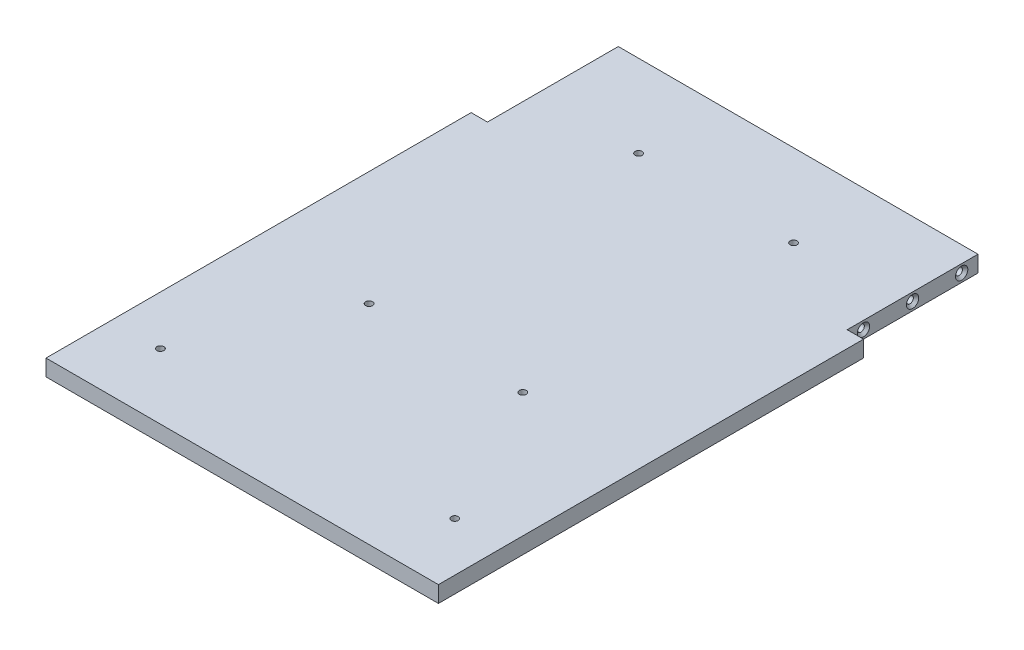
SolidWorks part; units mm, degrees
ref_plane "Front Plane" through (0, 0, 0) normal (0, 0, 1) x (1, 0, 0)
ref_plane "Top Plane" through (0, 0, 0) normal (0, 1, 0) x (1, 0, 0)
ref_plane "Right Plane" through (0, 0, 0) normal (1, 0, 0) x (0, 0, -1)
sketch "Sketch1" plane through (0, 0, 0) normal (0, 1, 0) x (1, 0, 0)
  line L0 (-6.35, 0) -> (-6.35, -50.8)
  line L1 (-6.35, 0) -> (-146.05, 0)
  line L2 (0, -50.8) -> (0, -215.9)
  line L3 (0, -215.9) -> (-152.4, -215.9)
  line L4 (-152.4, -50.8) -> (-152.4, -215.9)
  line L5 (-6.35, -50.8) -> (0, -50.8)
  line L6 (-146.05, 0) -> (-146.05, -50.8)
  line L7 (-146.05, -50.8) -> (-152.4, -50.8)
  point P7 (-3.175, -50.8)
  dimension "D1" = 152.4
  dimension "D2" = 215.9
  dimension "D3" = 50.8
  dimension "D4" = 6.35
  dimension "D5" = 6.35
  dimension "D6" = 50.8
extrude "Boss-Extrude1" add sketch "Sketch1" along normal blind 6.35
sketch "Sketch2" plane through (-6.35, 0, 0) normal (1, 0, 0) x (0, 0, -1)
  line L0 (-50.8, 6.35) -> (-50.8, 0) construction
  line L1 (-50.8, 6.35) -> (-50.8, 0) construction
  line L2 (-50.8, 0) -> (0, 0) construction
  circle A0 centre (-44.45, 3.175) radius 1.8288
  circle A1 centre (-25.4, 3.175) radius 1.8288
  circle A2 centre (-6.35, 3.175) radius 1.8288
  dimension "D4" = 3.175
  dimension "D5" = 3.175
  dimension "D6" = 3.6576
  dimension "D7" = 3.6576
  dimension "D8" = 3.6576
  dimension "D1" = 6.35
  dimension "D2" = 25.4
  dimension "D3" = 44.45
hole_wizard "#6-32 Tapped Hole1" positions "Sketch3" profile "Sketch4" tap size "#6-32" standard "ANSI Inch"
sketch "Sketch3" plane through (-6.35, 0, 0) normal (1, 0, 0) x (0, 0, -1)
  point P0 (-44.45, 3.175)
  point P3 (-25.4, 3.175)
  point P6 (-6.35, 3.175)
sketch "Sketch4" plane through (-6.35, 3.175, 44.45) normal (0, 1, 0) x (0, 0, -1)
  line L0 (0, 0) -> (0, 12.7)
  line L1 (0, 12.7) -> (1.3525, 11.8873)
  line L2 (1.3525, 11.8873) -> (1.3525, 1.0351)
  line L3 (1.3525, 1.0351) -> (2.3876, 0)
  line L5 (2.3876, 0) -> (0, 0)
  line L6 (-1.3525, 1.0351) -> (-2.3876, 0) construction
  line L10 (0, 12.7) -> (-1.3526, 11.8873) construction
  line L11 (0, -6.35) -> (0, 107.95) construction
  dimension "Tap Drill Dia." = 2.7051
  dimension "Tap Drill Depth" = 12.7
  dimension "Near C'Sink Dia." = 4.7752
  dimension "Near C'Sink Angle" = 90
  dimension "Drill Angle" = 118
cosmetic thread "Hole Thread1"
cosmetic thread "Hole Thread2"
cosmetic thread "Hole Thread3"
sketch "Sketch5" plane through (-146.05, 0, 0) normal (-1, 0, 0) x (0, 0, 1)
  circle A0 centre (6.35, 3.175) radius 1.8288
  circle A1 centre (25.4, 3.175) radius 1.8288
  circle A2 centre (44.45, 3.175) radius 1.8288
  dimension "D1" = 3.6576
  dimension "D2" = 3.6576
  dimension "D3" = 3.6576
hole_wizard "#6-32 Tapped Hole2" positions "Sketch6" profile "Sketch7" tap size "#6-32" standard "ANSI Inch"
sketch "Sketch6" plane through (-146.05, 0, 0) normal (-1, 0, 0) x (0, 0, 1)
  point P0 (6.35, 3.175)
  point P3 (25.4, 3.175)
  point P6 (44.45, 3.175)
sketch "Sketch7" plane through (-146.05, 3.175, 6.35) normal (0, 1, 0) x (0, 0, 1)
  line L0 (0, 0) -> (0, 12.7)
  line L1 (0, 12.7) -> (1.3525, 11.8873)
  line L2 (1.3525, 11.8873) -> (1.3525, 1.0351)
  line L3 (1.3525, 1.0351) -> (2.3876, 0)
  line L5 (2.3876, 0) -> (0, 0)
  line L6 (-1.3525, 1.0351) -> (-2.3876, 0) construction
  line L10 (0, 12.7) -> (-1.3526, 11.8873) construction
  line L11 (0, -6.35) -> (0, 107.95) construction
  dimension "Tap Drill Dia." = 2.7051
  dimension "Tap Drill Depth" = 12.7
  dimension "Near C'Sink Dia." = 4.7752
  dimension "Near C'Sink Angle" = 90
  dimension "Drill Angle" = 118
cosmetic thread "Hole Thread4"
cosmetic thread "Hole Thread5"
cosmetic thread "Hole Thread6"
sketch "Sketch8" plane through (0, 6.35, 0) normal (0, 1, 0) x (1, 0, 0)
  line L0 (0, -215.9) -> (0, -50.8) construction
  line L1 (-152.4, -215.9) -> (0, -215.9) construction
  circle A0 centre (-48.26, -134.874) radius 1.8288
  circle A1 centre (-107.95, -134.874) radius 1.8288
  dimension "D1" = 48.26
  dimension "D2" = 81.026
  dimension "D3" = 59.69
  dimension "D4" = 81.026
  dimension "D5" = 3.6576
  dimension "D6" = 3.6576
sketch "Sketch9" plane through (0, 6.35, 0) normal (0, 1, 0) x (1, 0, 0)
  line L0 (-152.4, -215.9) -> (0, -215.9) construction
  line L1 (-152.4, -50.8) -> (-152.4, -215.9) construction
  circle A0 centre (-133.35, -190.5) radius 1.8288
  circle A1 centre (-19.05, -190.5) radius 1.8288
  dimension "D1" = 114.3
  dimension "D2" = 25.4
  dimension "D3" = 19.05
  dimension "D4" = 3.6576
  dimension "D5" = 3.6576
hole_wizard "#6-32 Tapped Hole3" positions "Sketch12" profile "Sketch13" tap size "#6-32" standard "ANSI Inch" end condition up to next
sketch "Sketch12" plane through (0, 6.35, 0) normal (0, 1, 0) x (1, 0, 0)
  point P0 (-133.35, -190.5)
  point P3 (-19.05, -190.5)
sketch "Sketch13" plane through (-133.35, 6.35, 190.5) normal (1, 0, 0) x (0, 0, 1)
  line L0 (0, 0) -> (0, 6.35)
  line L1 (0, 6.35) -> (1.3525, 6.35)
  line L2 (1.3525, 6.35) -> (1.3525, 0)
  line L5 (1.3525, 0) -> (0, 0)
  line L11 (0, -6.35) -> (0, 107.95) construction
  dimension "Thru Tap Drill Dia." = 2.7051
  dimension "Thru Tap Drill Depth" = 6.35
cosmetic thread "Hole Thread7"
cosmetic thread "Hole Thread8"
hole_wizard "#6-32 Tapped Hole4" positions "Sketch14" profile "Sketch15" tap size "#6-32" standard "ANSI Inch" end condition up to next
sketch "Sketch14" plane through (0, 6.35, 0) normal (0, 1, 0) x (1, 0, 0)
  point P0 (-107.95, -134.874)
  point P3 (-48.26, -134.874)
sketch "Sketch15" plane through (-107.95, 6.35, 134.874) normal (1, 0, 0) x (0, 0, 1)
  line L0 (0, 0) -> (0, 6.35)
  line L1 (0, 6.35) -> (1.3525, 6.35)
  line L2 (1.3525, 6.35) -> (1.3525, 0)
  line L5 (1.3525, 0) -> (0, 0)
  line L11 (0, -6.35) -> (0, 107.95) construction
  dimension "Thru Tap Drill Dia." = 2.7051
  dimension "Thru Tap Drill Depth" = 6.35
cosmetic thread "Hole Thread9"
cosmetic thread "Hole Thread10"
sketch "Sketch16" plane through (0, 6.35, 0) normal (0, 1, 0) x (1, 0, 0)
  line L0 (-6.35, -50.8) -> (-6.35, 0) construction
  line L1 (-6.35, 0) -> (-146.05, 0) construction
  circle A0 centre (-45.974, -32.004) radius 1.8288
  circle A1 centre (-106.172, -32.004) radius 1.8288
  dimension "D1" = 39.624
  dimension "D2" = 32.004
  dimension "D3" = 60.198
  dimension "D4" = 32.004
  dimension "D5" = 3.6576
  dimension "D6" = 3.6576
hole_wizard "#6-32 Tapped Hole5" positions "Sketch19" profile "Sketch18" tap size "#6-32" standard "ANSI Inch" end condition up to next
sketch "Sketch19" plane through (0, 6.35, 0) normal (0, 1, 0) x (1, 0, 0)
  point P0 (-106.172, -32.004)
  point P3 (-45.974, -32.004)
sketch "Sketch18" plane through (-106.172, 6.35, 32.004) normal (1, 0, 0) x (0, 0, 1)
  line L0 (0, 0) -> (0, 6.35)
  line L1 (0, 6.35) -> (1.3525, 6.35)
  line L2 (1.3525, 6.35) -> (1.3525, 0)
  line L5 (1.3525, 0) -> (0, 0)
  line L11 (0, -6.35) -> (0, 107.95) construction
  dimension "Thru Tap Drill Dia." = 2.7051
  dimension "Thru Tap Drill Depth" = 6.35
cosmetic thread "Hole Thread11"
cosmetic thread "Hole Thread12"
